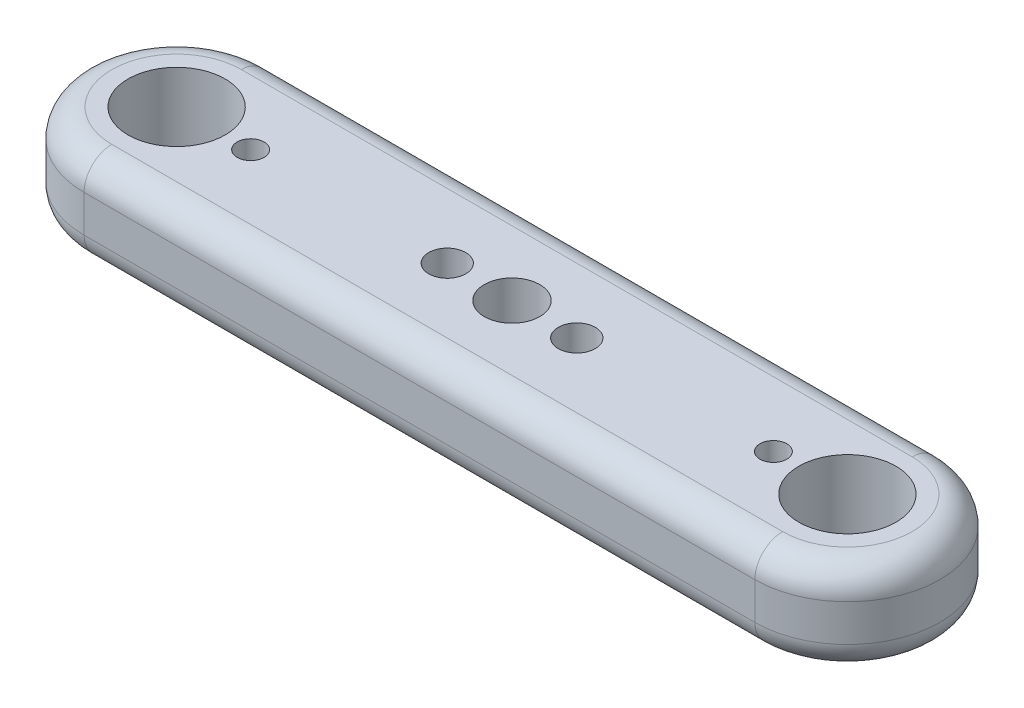
SolidWorks part; units mm, degrees
ref_plane "Front Plane" through (0, 0, 0) normal (0, 0, 1) x (1, 0, 0)
ref_plane "Top Plane" through (0, 0, 0) normal (0, 1, 0) x (1, 0, 0)
ref_plane "Right Plane" through (0, 0, 0) normal (1, 0, 0) x (0, 0, -1)
sketch "Sketch2" plane through (0, 0, 0) normal (0, 1, 0) x (1, 0, 0)
  line L4 (-36.25, 10) -> (36.25, 10)
  line L10 (36.25, -10) -> (-36.25, -10)
  arc A1 (0, -5) -> (0, 5) centre (0, 0) ccw
  circle A5 centre (0, 0) radius 5
  circle A6 centre (-36.25, 0) radius 5
  circle A7 centre (36.25, 0) radius 5
  arc A8 (-36.25, 10) -> (-36.25, -10) centre (-36.25, 0) ccw
  arc A9 (36.25, -10) -> (36.25, 10) centre (36.25, 0) ccw
  circle A10 centre (-36.25, 0) radius 10 construction
  circle A11 centre (36.25, 0) radius 10 construction
  point P3 (-19.375, 0)
  dimension "D1" = 5
  dimension "D2" = 5
extrude "Boss-Extrude1" add sketch "Sketch2" along normal blind 10 contours L10 A9 L4 A8 A5 A1 A6 A7 region at (0, 0, -9.0536)
fillet "Fillet1" radius 3 8 edges at (-46.25, 0, 0) (0, 0, 10) (46.25, 0, 0) (-46.25, 10, 0) (0, 10, 10) (46.25, 10, 0) (0, 0, -10) (0, 10, -10)
sketch "Sketch3" plane through (0, 10, 0) normal (0, 1, 0) x (1, 0, 0)
  line L0 (0, 0) -> (-6.5, 0)
  line L1 (-6.5, 0) -> (7.6495, 0)
  circle A0 centre (0, 0) radius 5
  circle M5 centre (0, 0) radius 5
extrude "Boss-Extrude2" add sketch "Sketch3" against normal blind 10 contours L0 L1 M5 | L1 L0 M5 region at (0, 10, 2.1221) region at (0, 10, -2.1221)
sketch "Sketch4" plane through (0, 10, 0) normal (0, 1, 0) x (1, 0, 0)
  line L0 (0, 0) -> (-8.2, 0)
  line L1 (0, 0) -> (8.2, 0)
  circle A0 centre (-8.2, 0) radius 1.5
  circle A1 centre (8.2, 0) radius 1.5
sketch "Sketch5" plane through (0, 10, 0) normal (0, 1, 0) x (1, 0, 0)
  circle A0 centre (-36.25, 0) radius 4.5
  circle A1 centre (-36.25, 0) radius 5
  circle A2 centre (36.25, 0) radius 5
  circle A3 centre (36.25, 0) radius 4.5
extrude "Boss-Extrude3" add sketch "Sketch5" against normal up to surface (10 mm away) up to face at (0, 0, 0)
sketch "Sketch6" plane through (0, 10, 0) normal (0, 1, 0) x (1, 0, 0)
  line L0 (7, 0) -> (-7, 0)
  circle A1 centre (-7, 0) radius 2
  circle A2 centre (7, 0) radius 2
extrude "Cut-Extrude1" cut sketch "Sketch6" against normal blind 10 contours A1 | A2 region at (-8.9434, 10, 0) region at (7, 10, -1.9434)
sketch "Sketch7" plane through (0, 10, 0) normal (0, 1, 0) x (1, 0, 0)
  circle A0 centre (0, 0) radius 3
extrude "Cut-Extrude2" cut sketch "Sketch7" against normal blind 10
sketch "Sketch8" plane through (0, 10, 0) normal (0, 1, 0) x (1, 0, 0)
  circle A0 centre (-36.25, 0) radius 4.65
  circle A1 centre (36.25, 0) radius 4.65
extrude "Cut-Extrude3" cut sketch "Sketch8" against normal blind 17
sketch "Sketch9" plane through (0, 10, 0) normal (0, 1, 0) x (1, 0, 0)
  circle A0 centre (-36.25, 0) radius 5.25
  circle A1 centre (36.25, 0) radius 5.25
  circle A2 centre (-36.25, 0) radius 8
  circle A3 centre (36.25, 0) radius 8
  circle A4 centre (-28.25, 0) radius 1.45
  circle A5 centre (28.25, 0) radius 1.45
  circle M1 centre (-36.25, 0) radius 4.65
  circle M2 centre (36.25, 0) radius 4.65
extrude "Cut-Extrude4" cut sketch "Sketch9" against normal blind 10 contours M1 | M2 | A0 M1 | A1 M2 region at (-41.3515, 10, 0) region at (31.1485, 10, 0) region at (-36.25, 10, 0) region at (36.25, 10, 0)
extrude "Cut-Extrude5" cut sketch "Sketch9<3>" against normal blind 10 contours A2 A4 | A2 A4 | A3 A5 | A3 A5 region at (-28.8885, 10, 0) region at (-27.6589, 10, 0) region at (28.8885, 10, 0) region at (27.6589, 10, 0)
sketch "Sketch9<3>" plane through (0, 10, 0) normal (0, 1, 0) x (1, 0, 0) same geometry as "Sketch9"
